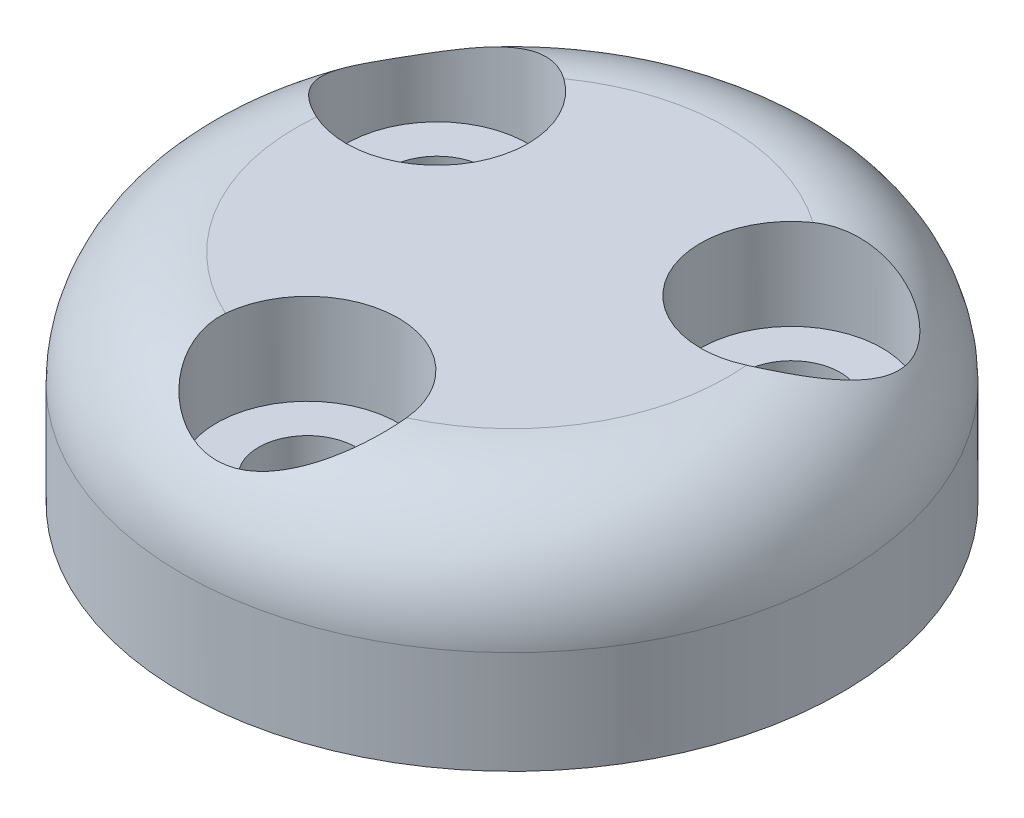
SolidWorks part; units mm, degrees
material "Stainless Steel (ferritic)"
ref_plane "Front Plane" through (0, 0, 0) normal (0, 0, 1) x (1, 0, 0)
ref_plane "Top Plane" through (0, 0, 0) normal (0, 1, 0) x (1, 0, 0)
ref_plane "Right Plane" through (0, 0, 0) normal (1, 0, 0) x (0, 0, -1)
sketch "Sketch1" plane through (0, 0, 0) normal (0, 1, 0) x (1, 0, 0)
  circle A0 centre (0, 0) radius 14.5
  dimension "D1" = 29
extrude "Boss-Extrude1" add sketch "Sketch1" along normal blind 9.525
sketch "Sketch2" plane through (0, 0, 0) normal (0, -1, 0) x (1, 0, 0)
  circle A0 centre (0, 0) radius 3.5
  dimension "D1" = 7
extrude "Cut-Extrude1" cut sketch "Sketch2" against normal blind 3.5
sketch "Sketch3" plane through (0, 3.5, 0) normal (0, -1, 0) x (1, 0, 0)
  circle A0 centre (0, 0) radius 3.125
  dimension "D1" = 6.25
extrude "Cut-Extrude2" cut sketch "Sketch3" against normal blind 5
hole_wizard "CBORE for M4 SHCS1" positions "Sketch5" profile "Sketch4" counterbore size "M4" standard "Ansi Metric" end condition through all
sketch "Sketch5" plane through (0, 9.525, 0) normal (0, 1, 0) x (-1, 0, 0)
  point P0 (0, 9)
  dimension "D1" = 9
sketch "Sketch4" plane through (0, 9.525, 9) normal (1, 0, 0) x (0, 0, 1)
  line L0 (0, 0) -> (0, 9.525)
  line L1 (0, 9.525) -> (2.15, 9.525)
  line L3 (2.15, 9.525) -> (2.15, 4)
  line L4 (2.15, 4) -> (4, 4)
  line L5 (4, 4) -> (4, 0)
  line L7 (4, 0) -> (0, 0)
  line L11 (0, -6.35) -> (0, 107.95) construction
  dimension "Thru Hole Dia." = 4.3
  dimension "Thru Hole Depth" = 9.525
  dimension "C'Bore Dia." = 8
  dimension "C'Bore Depth" = 4
pattern_circular "CirPattern1" count 3 over 360 about axis through (0, 9.525, 0) along (0, -1, 0) of "CBORE for M4 SHCS1"
fillet "Fillet1" radius 5 1 edges at (0, 9.525, 14.5)
sketch "Sketch6" plane through (0, 0, 0) normal (0, -1, 0) x (1, 0, 0)
  line L0 (0, 0) -> (-8.923, 1.1747) construction
  line L1 (-8.923, 1.1747) -> (-5.4789, 7.1402) construction
  line L2 (-5.4789, 7.1402) -> (0, 0) construction
  line L3 (0, 0) -> (-3.8867, 0) construction
  arc A0 (-3.3033, 8.3719) -> (-8.9019, -1.3252) centre (0, 0) ccw construction
  arc A1 (-11.4016, 1.5011) -> (-6.4444, 0.8484) centre (-8.923, 1.1747) ccw
  arc A3 (-7.0008, 9.1236) -> (-11.4016, 1.5011) centre (0, 0) ccw
  arc A4 (-3.9569, 5.1568) -> (-6.4444, 0.8484) centre (0, 0) ccw
  arc A5 (-3.9569, 5.1568) -> (-7.0008, 9.1236) centre (-5.4789, 7.1402) ccw
  dimension "D1" = 5
  dimension "D2" = 45
  dimension "D3" = 7.5
extrude "Cut-Extrude3" cut sketch "Sketch6" against normal blind 5
pattern_circular "CirPattern2" count 3 over 360 about axis through (0, 3.5, 0) along (0, -1, 0) of "Cut-Extrude3"
